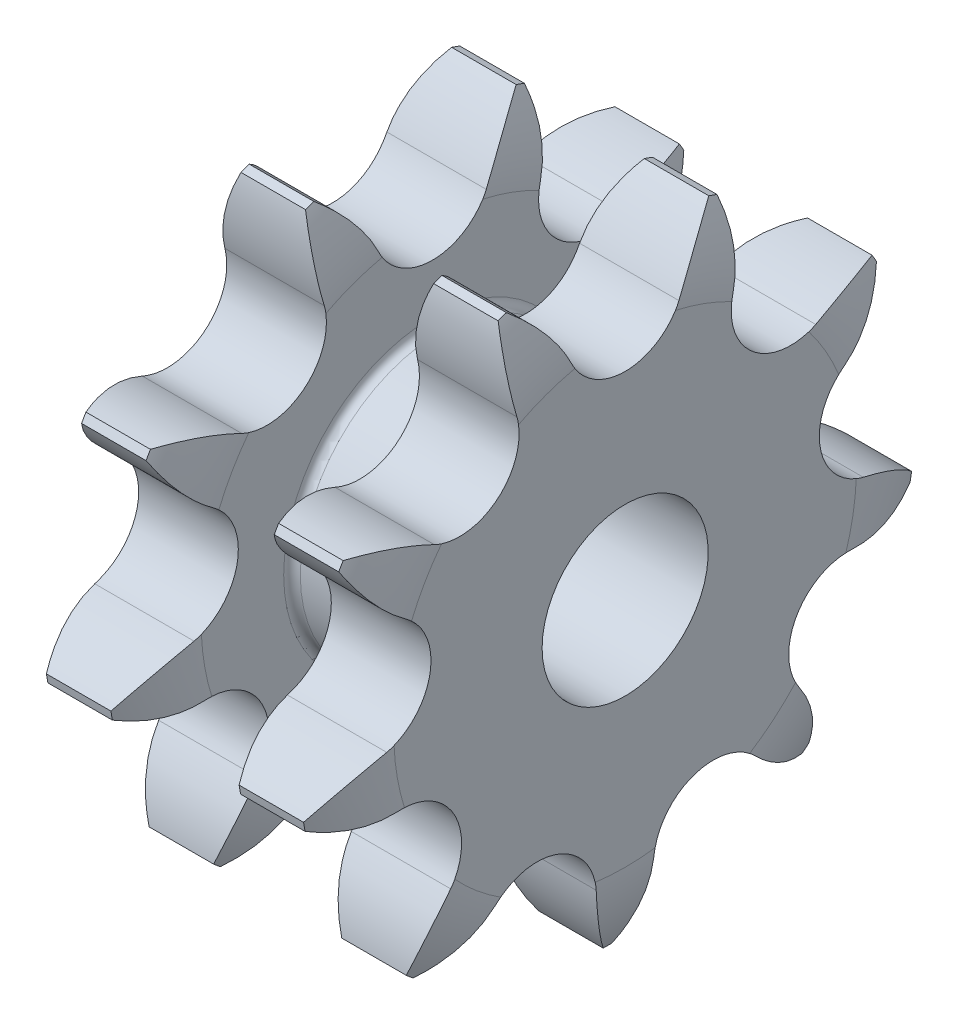
SolidWorks part; units mm, degrees
ref_plane "Plane1" through (0, 0, 0) normal (0, 0, 1) x (1, 0, 0)
ref_plane "Plane2" through (0, 0, 0) normal (0, 1, 0) x (1, 0, 0)
ref_plane "Plane3" through (0, 0, 0) normal (1, 0, 0) x (0, 0, -1)
sketch "Clipboard" plane through (0, 0, 0) normal (0, 1, 0) x (1, 0, 0)
  line L0 (0, 0) -> (12.5436, -1.9867)
  line L1 (-15, 0) -> (100, 0) construction
  line L2 (0, 0) -> (-0.8416, 0.9512)
  line L3 (0, 0) -> (-11.863, 4.5341)
  line L4 (0, 0) -> (3.0618, 0.4849)
  line L5 (0, 0) -> (-2.8109, -1.0484)
  line L6 (0, 0) -> (-17.5077, -11.8125)
  line L7 (-0.8416, 0.9512) -> (22.0505, 5.4009)
  line L8 (-76.2, 38.1) -> (-75.2, 38.1)
  line L9 (-73.4259, 41.6592) -> (-72.8306, 41.7344)
  line L10 (-73.4741, 12.7512) -> (-59.5541, 12.7512)
  circle A0 centre (0, 0) radius 4.255
  circle A1 centre (0, 0) radius 10.1515
  circle A2 centre (0, 0) radius 25
  dimension "Num_teeth" = 9
  dimension "Thickness" = 21.12
  dimension "Fillet_rad" = 0.6
sketch "BasProSke" plane through (0, 0, 0) normal (0, 1, 0) x (1, 0, 0)
  line L0 (-10, 0) -> (60, 0) construction
  line L1 (0, 0) -> (0, 16.7129)
  line L2 (0, 0) -> (21.12, 0)
  line L3 (21.12, 0) -> (21.12, 16.7129)
  line L4 (19.85, 22.2487) -> (1.27, 22.2487)
  arc A0 (0, 16.7129) -> (1.27, 22.2487) centre (12.7, 16.7129) cw
  arc A1 (21.12, 16.7129) -> (19.85, 22.2487) centre (8.42, 16.7129) ccw
  dimension "D1" = 12.7
  dimension "Thickness" = 21.12
  dimension "Diameter" = 44.4973
  dimension "G1" = 1.27
revolve "Base-Revolve" add sketch "BasProSke" angle 360 about L0
sketch "GrvSke" plane through (0, 0, 0) normal (0, 1, 0) x (1, 0, 0)
  line L0 (7.2, 16.7129) -> (7.2, 10.7515)
  line L1 (7.8, 10.1515) -> (13.32, 10.1515)
  line L2 (13.92, 10.7515) -> (13.92, 16.7129)
  line L3 (5.93, 22.2487) -> (15.19, 22.2487)
  line L4 (10.56, 0) -> (10.56, 52.07) construction
  line L5 (-10, 0) -> (60, 0) construction
  line L6 (0, 0) -> (35.56, 0) construction
  arc A0 (13.92, 16.7129) -> (15.19, 22.2487) centre (26.62, 16.7129) cw
  arc A1 (7.2, 16.7129) -> (5.93, 22.2487) centre (-5.5, 16.7129) ccw
  arc A2 (7.2, 10.7515) -> (7.8, 10.1515) centre (7.8, 10.7515) ccw
  arc A3 (13.32, 10.1515) -> (13.92, 10.7515) centre (13.32, 10.7515) ccw
  dimension "D1" = 12.7
  dimension "Diameter" = 44.4973
  dimension "Fillet_rad" = 0.6
  dimension "G1" = 1.27
  dimension "Grv_width" = 6.72
revolve "Groove" cut sketch "GrvSke" angle 360 about L6
sketch "TooCutSke" plane through (0, 0, 0) normal (1, 0, 0) x (0, 0, -1)
  line L0 (0, 18.6087) -> (3.8949, 16.7925) construction
  line L1 (0, 0) -> (0, 107) construction
  line L2 (0, 18.6087) -> (-10, 18.6087) construction
  line L3 (0, 18.6087) -> (-3.8949, 16.7925) construction
  arc A0 (3.8949, 16.7925) -> (7.8075, 21.3669) centre (14.0756, 12.0451) cw
  arc A1 (3.8949, 16.7925) -> (-3.8949, 16.7925) centre (0, 18.6087) cw
  arc A2 (-3.8949, 16.7925) -> (-7.8075, 21.3669) centre (-14.0756, 12.0451) ccw
  arc A3 (7.8075, 21.3669) -> (-7.8075, 21.3669) centre (0, 0) ccw
extrude "ToothCut" cut sketch "TooCutSke" along normal through all
pattern_circular "TeethCuts" count 9 every 40 about axis through (-10, 0, 0) along (1, 0, 0) of "ToothCut"
sketch "HubNeaOneSke" plane through (0, 0, 0) normal (-1, 0, 0) x (0, 0, 1)
  circle A0 centre (0, 0) radius 10.1515
  dimension "Diameter" = 20.303
extrude "HubNearOne" [suppressed] add sketch "HubNeaOneSke" along normal blind 2.2005
fillet "HubNearOneFillet" [suppressed] radius 0.6
sketch "HubNeaBotSke" plane through (0, 0, 0) normal (-1, 0, 0) x (0, 0, 1)
  circle A0 centre (0, 0) radius 10.1515
  dimension "Diameter" = 20.303
extrude "HubNearBoth" [suppressed] add sketch "HubNeaBotSke" along normal blind 1.1003
fillet "HubNearBothFillet" [suppressed] radius 0.6
ref_plane "FarPln" through (21.12, 0, 0) normal (1, 0, 0) x (0, 0, -1)
sketch "HubFarSke" plane through (21.12, 0, 0) normal (1, 0, 0) x (0, 0, -1)
  circle A0 centre (0, 0) radius 10.1515
  dimension "Diameter" = 20.303
extrude "HubFar" [suppressed] add sketch "HubFarSke" along normal blind 1.1003
fillet "HubFarFillet" [suppressed] radius 0.6
sketch "BorSke" plane through (0, 0, 0) normal (1, 0, 0) x (0, 0, -1)
  circle A0 centre (0, 0) radius 6
  dimension "Diameter" = 12
extrude "Bore" cut sketch "BorSke" along normal mid plane 46.641
sketch "KeySke" plane through (0, 0, 0) normal (1, 0, 0) x (0, 0, -1)
  line L0 (-1, 0) -> (-1, 7)
  line L1 (-1, 7) -> (1, 7)
  line L2 (1, 7) -> (1, 0)
  line L3 (0, 0) -> (0, 34) construction
  line L4 (-1, 0) -> (1, 0)
  dimension "Offset" = 7
  dimension "Width" = 2
extrude "Keyway" [suppressed] cut sketch "KeySke" along normal mid plane 46.641
pattern_circular "Keyway2" [suppressed] count 2 every 90 about axis through (-10, 0, 0) along (1, 0, 0) reverse direction yes
equation "' \"Pitch@Clipboard\" = 12.7"
equation "' \"Num_strands@Clipboard\" = 2"
equation "' \"Num_teeth@Clipboard\" = 9"
equation "' \"Hub_dia@Clipboard\" = 50"
equation "' \"Overall_len@Clipboard\" = 3"
equation "' \"Diameter@BorSke\" = 12"
equation "' \"T_dim@Clipboard\" = 1"
equation "' \"Width@KeySke\" = 2"
equation "' \"Dr@Clipboard\" = 8.51"
equation "' \"Face_width@Clipboard\" = 7.2"
equation "' \"Side_radius@Clipboard\" = 12.7"
equation "' \"Side_relief@Clipboard\" = 1.27"
equation "' \"Transv_pitch@Clipboard\" = 13.92"
equation "' \"Show_teeth@Clipboard\" = 9"
equation "' \"Fillet_rad@Clipboard\" = 0.6"
equation "' \"Plate_wid@Clipboard\" = 11.8"
equation "\"Num_teeth@Clipboard\" = int( \"Num_teeth@Clipboard\" )"
equation "\"Num_teeth@Clipboard\" = ((sgn( \"Num_teeth@Clipboard\" - 5.0)+1)*( \"Num_teeth@Clipboard\" - 5.0))/2 +5.0"
equation "\"Num_teeth@Clipboard\" = ((sgn( \"Num_teeth@Clipboard\" - 200.0)-1)*( \"Num_teeth@Clipboard\" - 200.0))/-2 +200.0"
equation "\"MHD@Clipboard\" = \"Pitch@Clipboard\" * (1.0 / tan(3.14159265 / \"Num_teeth@Clipboard\" )) - 1.05 * \"Plate_wid@Clipboard\" - 2.0 * \"Fillet_rad@Clipboard\" - 1.0"
equation "\"Thickness@Clipboard\"  = \"Face_width@Clipboard\" + (\"Num_strands@Clipboard\" - 1) * \"Transv_pitch@Clipboard\""
equation "\"OAL@Clipboard\" = \"Thickness@Clipboard\" + 2 * \"Fillet_rad@Clipboard\" + 1"
equation "\"MHD@Clipboard\" = ((sgn( \"MHD@Clipboard\" - \"Hub_dia@Clipboard\" )-1)*( \"MHD@Clipboard\" - \"Hub_dia@Clipboard\" ))/-2+ \"Hub_dia@Clipboard\""
equation "\"OAL@Clipboard\" = ((sgn( \"OAL@Clipboard\" - \"Overall_len@Clipboard\" )+1)*( \"OAL@Clipboard\" - \"Overall_len@Clipboard\" ))/2 + \"Overall_len@Clipboard\" + 0.0005"
equation "\"Num_teeth@TeethCuts\" = int( \"Show_teeth@Clipboard\" ) + 1"
equation "\"Num_teeth@TeethCuts\" = ((sgn( \"Num_teeth@TeethCuts\" - \"Num_teeth@Clipboard\" )-1)*( \"Num_teeth@TeethCuts\" - \"Num_teeth@Clipboard\" ))/-2+ \"Num_teeth@Clipboard\""
equation "\"Num_teeth@TeethCuts\" = ((sgn( \"Num_teeth@TeethCuts\" - 2.0)+1)*( \"Num_teeth@TeethCuts\" - 2.0))/2 +2.0"
equation "\"Angle@TeethCuts\" = 360.0 / \"Num_teeth@Clipboard\""
equation "\"Seat_radius@TooCutSke\" = ( \"Pitch@Clipboard\" / 2.0) / sin(3.14159265 / \"Num_teeth@Clipboard\" ) - \"Dr@Clipboard\" / 2.0 + \"Dr@Clipboard\" * 0.505"
equation "\"R1@TooCutSke\"  = \"Dr@Clipboard\" * 0.505"
equation "\"X@TooCutSke\" = 140.0 - (90.0 / \"Num_teeth@Clipboard\")"
equation "\"R2@TooCutSke\" = 0.12 * \"Dr@Clipboard\" * ( \"Num_teeth@Clipboard\" + 2.0)"
equation "\"Overcut@TooCutSke\" = 0.5 + 0.625 * \"Pitch@Clipboard\" - 0.5 * \"Dr@Clipboard\"  +  \"Pitch@Clipboard\" / 2.0 / sin(3.14159265 / \"Num_teeth@Clipboard\" )"
equation "\"Diameter@BasProSke\" = 2.0 * ( 0.625 * \"Pitch@Clipboard\" - 0.5 * \"Dr@Clipboard\"  +  \"Pitch@Clipboard\" / 2.0 / sin(3.14159265 / \"Num_teeth@Clipboard\" ))"
equation "\"Thickness@BasProSke\"  = \"Thickness@Clipboard\""
equation "\"G1@BasProSke\" =  \"Side_relief@Clipboard\""
equation "\"G2@BasProSke\" =  \"Side_relief@Clipboard\""
equation "\"D1@BasProSke\" =  \"Side_radius@Clipboard\""
equation "\"Diameter@GrvSke\" = \"Diameter@BasProSke\""
equation "\"G1@GrvSke\" = \"Side_relief@Clipboard\""
equation "\"D1@GrvSke\" = \"Side_radius@Clipboard\""
equation "\"Grv_diam@GrvSke\" =  \"Pitch@Clipboard\" * (1.0 / tan(3.14159265 / \"Num_teeth@Clipboard\" ))- 1.05 * \"Plate_wid@Clipboard\" - 2.0 * \"Fillet_rad@Clipboard\" - 1.0"
equation "\"Grv_width@GrvSke\" =  \"Transv_pitch@Clipboard\" - \"Face_width@Clipboard\""
equation "\"Offset@GrvSke\" = \"Grv_width@GrvSke\" / 2.0 + \"Face_width@Clipboard\""
equation "\"Fillet_rad@GrvSke\" = \"Fillet_rad@Clipboard\""
equation "\"Diameter@HubNeaOneSke\" = \"MHD@Clipboard\""
equation "\"Length@HubNearOne\" = \"OAL@Clipboard\" - \"Thickness@BasProSke\""
equation "\"Diameter@HubNeaBotSke\" = \"MHD@Clipboard\""
equation "\"Length@HubNearBoth\" = ( \"OAL@Clipboard\" - \"Thickness@BasProSke\" ) / 2.0"
equation "\"D1@HubNearOneFillet\" = \"Fillet_rad@Clipboard\""
equation "\"D1@HubNearBothFillet\" = \"Fillet_rad@Clipboard\""
equation "\"Thickness@FarPln\" = \"Thickness@BasProSke\""
equation "\"Diameter@HubFarSke\" = \"MHD@Clipboard\""
equation "\"Length@HubFar\" = ( \"OAL@Clipboard\" - \"Thickness@BasProSke\" ) / 2.0"
equation "\"D1@HubFarFillet\" = \"Fillet_rad@Clipboard\""
equation "\"D1@Bore\" = \"OAL@Clipboard\" * 2.0"
equation "\"D1@Keyway\" = \"OAL@Clipboard\" * 2.0"
equation "\"Offset@KeySke\" = \"T_dim@Clipboard\" + \"Diameter@BorSke\" / 2.0"
